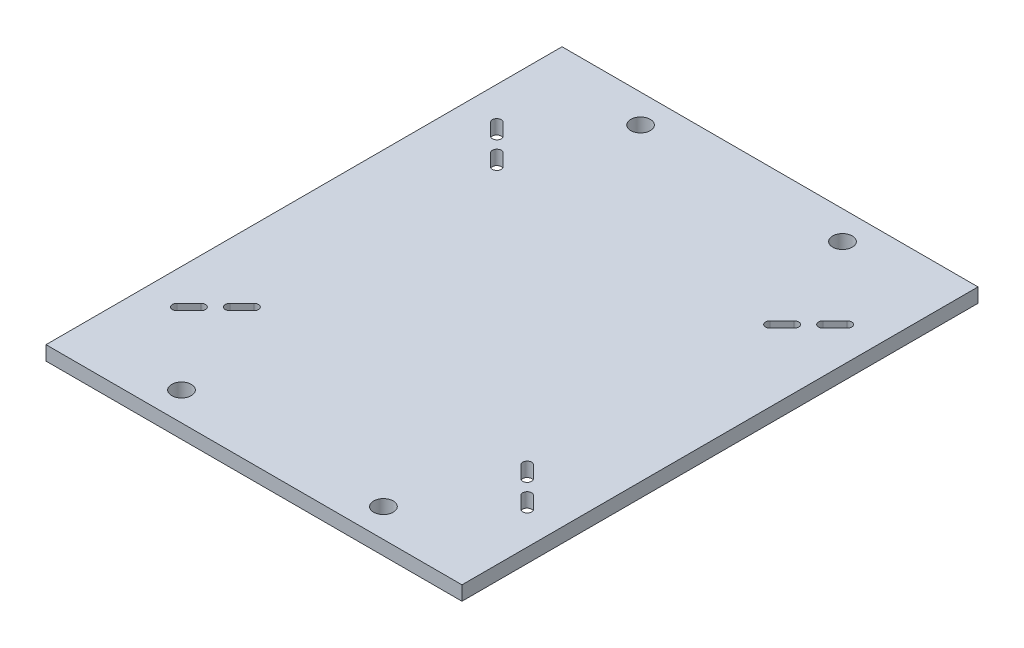
SolidWorks part; units mm, degrees
material "6061-T6 (SS)"
ref_plane "Front Plane" through (0, 0, 0) normal (0, 0, 1) x (1, 0, 0)
ref_plane "Top Plane" through (0, 0, 0) normal (0, 1, 0) x (1, 0, 0)
ref_plane "Right Plane" through (0, 0, 0) normal (1, 0, 0) x (0, 0, -1)
sketch "Sketch1" plane through (0, 0, 0) normal (0, 1, 0) x (1, 0, 0)
  line L1 (0, 0) -> (185.4, 0)
  line L2 (0, 0) -> (0, -230)
  line L3 (0, -230) -> (185.4, -230)
  line L4 (185.4, 0) -> (185.4, -230)
  dimension "D1" = 185.4
  dimension "D2" = 230
extrude "base plate" add sketch "Sketch1" against normal blind 6.35
sketch "center lines" plane through (0, 0, 0) normal (0, 1, 0) x (1, 0, 0)
  line L0 (92.7, 0) -> (92.7, -230) construction
  line L1 (185.4, 0) -> (0, 0) construction
  line L2 (0, -230) -> (185.4, -230) construction
  line L3 (0, -115) -> (185.4, -115) construction
  line L4 (0, 0) -> (0, -230) construction
  line L5 (185.4, -230) -> (185.4, 0) construction
sketch "Sketch3" plane through (0, 0, 0) normal (0, 1, 0) x (1, 0, 0)
  line L0 (1.825, -188.3487) -> (12.6013, -199.125)
  line L1 (12.6013, -199.125) -> (46.7263, -165)
  line L2 (46.7263, -165) -> (35.95, -154.2237)
  line L3 (35.95, -154.2237) -> (1.825, -188.3487)
  line L4 (14.6222, -186.3278) -> (20.0104, -180.9396) construction
  line L5 (13.208, -184.9135) -> (18.5962, -179.5254)
  line L6 (16.0365, -187.742) -> (21.4246, -182.3538)
  line L7 (0, -230) -> (185.4, -230) construction
  line L8 (31.8191, -169.1309) -> (26.4309, -174.5191) construction
  line L9 (33.2333, -170.5451) -> (27.8451, -175.9333)
  line L10 (92.7, 0) -> (92.7, -230) construction
  line L11 (0, -115) -> (185.4, -115) construction
  line L12 (46.7263, -65) -> (35.95, -75.7763)
  line L13 (12.6013, -30.875) -> (46.7263, -65)
  line L14 (1.825, -41.6513) -> (12.6013, -30.875)
  line L15 (35.95, -75.7763) -> (1.825, -41.6513)
  line L16 (172.7987, -30.875) -> (138.6737, -65)
  line L17 (183.575, -41.6513) -> (172.7987, -30.875)
  line L18 (149.45, -75.7763) -> (183.575, -41.6513)
  line L19 (138.6737, -65) -> (149.45, -75.7763)
  line L20 (138.6737, -165) -> (149.45, -154.2237)
  line L21 (172.7987, -199.125) -> (138.6737, -165)
  line L22 (183.575, -188.3487) -> (172.7987, -199.125)
  line L23 (149.45, -154.2237) -> (183.575, -188.3487)
  line L24 (30.4049, -167.7167) -> (25.0167, -173.1049)
  line L25 (14.6222, -43.6722) -> (20.0104, -49.0604) construction
  line L26 (13.208, -45.0865) -> (18.5962, -50.4746)
  line L27 (16.0365, -42.258) -> (21.4246, -47.6462)
  line L28 (31.8191, -60.8691) -> (26.4309, -55.4809) construction
  line L29 (33.2333, -59.4549) -> (27.8451, -54.0667)
  line L30 (30.4049, -62.2833) -> (25.0167, -56.8951)
  line L31 (170.7778, -43.6722) -> (165.3896, -49.0604) construction
  line L32 (172.192, -45.0865) -> (166.8038, -50.4746)
  line L33 (169.3635, -42.258) -> (163.9754, -47.6462)
  line L34 (153.5809, -60.8691) -> (158.9691, -55.4809) construction
  line L35 (152.1667, -59.4549) -> (157.5549, -54.0667)
  line L36 (154.9951, -62.2833) -> (160.3833, -56.8951)
  line L37 (153.5809, -169.1309) -> (158.9691, -174.5191) construction
  line L38 (152.1667, -170.5451) -> (157.5549, -175.9333)
  line L39 (154.9951, -167.7167) -> (160.3833, -173.1049)
  line L40 (170.7778, -186.3278) -> (165.3896, -180.9396) construction
  line L41 (172.192, -184.9135) -> (166.8038, -179.5254)
  line L42 (169.3635, -187.742) -> (163.9754, -182.3538)
  line L43 (35.95, -165) -> (35.95, -154.2237)
  line L44 (46.7263, -165) -> (35.95, -165)
  line L45 (35.95, -65) -> (35.95, -75.7763)
  line L46 (46.7263, -65) -> (35.95, -65)
  line L47 (149.45, -65) -> (149.45, -75.7763)
  line L48 (138.6737, -65) -> (149.45, -65)
  line L49 (149.45, -165) -> (149.45, -154.2237)
  line L50 (138.6737, -165) -> (149.45, -165)
  line L53 (185.4, 0) -> (0, 0) construction
  arc A0 (13.208, -184.9135) -> (16.0365, -187.742) centre (14.6222, -186.3278) ccw
  arc A1 (21.4246, -182.3538) -> (18.5962, -179.5254) centre (20.0104, -180.9396) ccw
  arc A2 (33.2333, -170.5451) -> (30.4049, -167.7167) centre (31.8191, -169.1309) ccw
  arc A3 (25.0167, -173.1049) -> (27.8451, -175.9333) centre (26.4309, -174.5191) ccw
  arc A4 (13.208, -45.0865) -> (16.0365, -42.258) centre (14.6222, -43.6722) cw
  arc A5 (21.4246, -47.6462) -> (18.5962, -50.4746) centre (20.0104, -49.0604) cw
  arc A6 (33.2333, -59.4549) -> (30.4049, -62.2833) centre (31.8191, -60.8691) cw
  arc A7 (25.0167, -56.8951) -> (27.8451, -54.0667) centre (26.4309, -55.4809) cw
  arc A8 (172.192, -45.0865) -> (169.3635, -42.258) centre (170.7778, -43.6722) ccw
  arc A9 (163.9754, -47.6462) -> (166.8038, -50.4746) centre (165.3896, -49.0604) ccw
  arc A10 (152.1667, -59.4549) -> (154.9951, -62.2833) centre (153.5809, -60.8691) ccw
  arc A11 (160.3833, -56.8951) -> (157.5549, -54.0667) centre (158.9691, -55.4809) ccw
  arc A12 (152.1667, -170.5451) -> (154.9951, -167.7167) centre (153.5809, -169.1309) cw
  arc A13 (160.3833, -173.1049) -> (157.5549, -175.9333) centre (158.9691, -174.5191) cw
  arc A14 (172.192, -184.9135) -> (169.3635, -187.742) centre (170.7778, -186.3278) cw
  arc A15 (163.9754, -182.3538) -> (166.8038, -179.5254) centre (165.3896, -180.9396) cw
  point P29 (17.3163, -183.6337)
  point P36 (29.125, -171.825)
  point P44 (17.3163, -46.3663)
  point P51 (29.125, -58.175)
  point P58 (168.0837, -46.3663)
  point P65 (156.275, -58.175)
  point P72 (156.275, -171.825)
  point P79 (168.0837, -183.6337)
  point P84 (21.4246, -179.5254)
  point P85 (25.0167, -175.9333)
  dimension "D6" = 2
  dimension "D10" = 5.08
  dimension "D9" = 5.842
  dimension "D1" = 48.26
  dimension "D2" = 15.24
  dimension "D3" = 45
  dimension "D4" = 100
  dimension "D5" = 113.5
  dimension "D7" = 7.62
  dimension "D8" = 7.62
extrude "slots" cut sketch "Sketch3" against normal through all contours A5 L27 A4 L26 | L33 A9 L32 A8 | L36 A11 L35 A10 | A13 L39 A12 L38 | A15 L42 A14 L41 | L6 A1 L5 A0 | L24 A3 L9 A2 | L30 A7 L29 A6 region at (17.3163, 0, 46.3663) region at (168.0837, 0, 46.3663) region at (156.275, 0, 58.175) region at (156.275, 0, 171.825) region at (168.0837, 0, 183.6337)
hole_wizard "Feet connection hole" positions "Sketch6" profile "Sketch7" hole size "1/4-20" standard "PEM® Inch" end condition through all
sketch "Sketch6" plane through (0, 0, 0) normal (0, 1, 0) x (1, 0, 0)
  line L0 (0, -230) -> (185.4, -230) construction
  line L3 (185.4, 0) -> (0, 0) construction
  line L4 (92.7, 0) -> (92.7, -230) construction
  point P3 (47.7, -217.3)
  point P19 (137.7, -12.7)
  point P33 (47.7, -12.7)
  point P37 (137.7, -217.3)
  dimension "D1" = 12.7
  dimension "D2" = 90
  dimension "D3" = 45
  dimension "D4" = 12.7
sketch "Sketch7" plane through (47.7, 0, 217.3) normal (1, 0, 0) x (0, 0, 1)
  line L0 (0, 0) -> (0, 6.35)
  line L1 (0, 6.35) -> (4.3688, 6.35)
  line L2 (4.3688, 6.35) -> (4.3688, 0)
  line L5 (4.3688, 0) -> (0, 0)
  line L11 (0, -6.35) -> (0, 107.95) construction
  dimension "Thru Hole Dia." = 8.7376
  dimension "Thru Hole Depth" = 6.35
ref_plane "Center Plane" through (0, 0, 115) normal (0, 0, 1) x (1, 0, 0)
